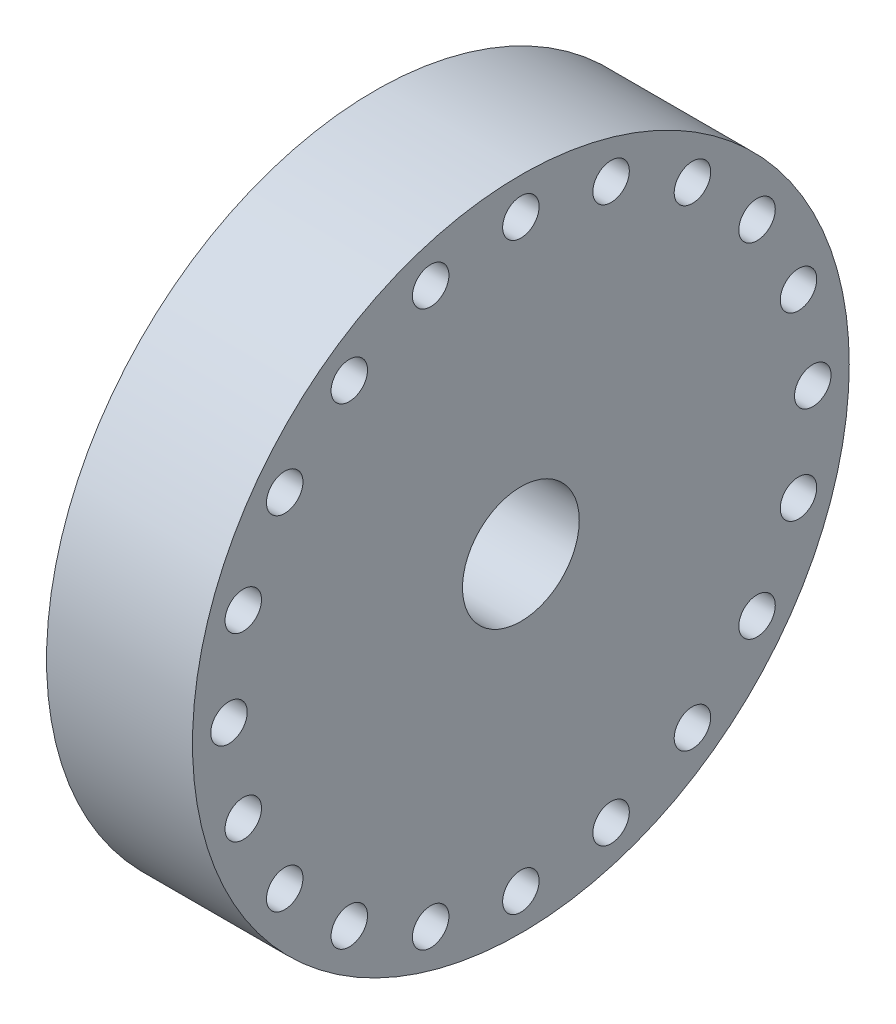
SolidWorks part; units mm, degrees
ref_plane "Front Plane" through (0, 0, 0) normal (0, 0, 1) x (1, 0, 0)
ref_plane "Top Plane" through (0, 0, 0) normal (0, 1, 0) x (1, 0, 0)
ref_plane "Right Plane" through (0, 0, 0) normal (1, 0, 0) x (0, 0, -1)
sketch "Sketch1" plane through (0, 0, 0) normal (1, 0, 0) x (0, 0, -1)
  circle A0 centre (0, 0) radius 7.1438
  circle A1 centre (0, 0) radius 6.35 construction
  circle A2 centre (0, 6.35) radius 0.3969
  circle A3 centre (1.9623, 6.0392) radius 0.3969
  circle A4 centre (3.7324, 5.1373) radius 0.3969
  circle A5 centre (5.1373, 3.7324) radius 0.3969
  circle A6 centre (6.0392, 1.9623) radius 0.3969
  circle A7 centre (6.35, 0) radius 0.3969
  circle A8 centre (6.0392, -1.9623) radius 0.3969
  circle A9 centre (5.1373, -3.7324) radius 0.3969
  circle A10 centre (3.7324, -5.1373) radius 0.3969
  circle A11 centre (1.9623, -6.0392) radius 0.3969
  circle A12 centre (0, -6.35) radius 0.3969
  circle A13 centre (-1.9623, -6.0392) radius 0.3969
  circle A14 centre (-3.7324, -5.1373) radius 0.3969
  circle A15 centre (-5.1373, -3.7324) radius 0.3969
  circle A16 centre (-6.0392, -1.9623) radius 0.3969
  circle A17 centre (-6.35, 0) radius 0.3969
  circle A18 centre (-6.0392, 1.9623) radius 0.3969
  circle A19 centre (-5.1373, 3.7324) radius 0.3969
  circle A20 centre (-3.7324, 5.1373) radius 0.3969
  circle A21 centre (-1.9623, 6.0392) radius 0.3969
  dimension "D1" = 20
  dimension "D2" = 14.2875
  dimension "D3" = 0.7937
  dimension "D4" = 12.7
extrude "Boss-Extrude1" add sketch "Sketch1" along normal blind 3.175
sketch "Sketch2" plane through (3.175, 0, 0) normal (1, 0, 0) x (0, 0, -1)
  circle A0 centre (0, 0) radius 1.27
  dimension "D1" = 2.54
extrude "Cut-Extrude1" cut sketch "Sketch2" against normal through all
sketch "Sketch3" plane through (3.175, 0, 0) normal (1, 0, 0) x (0, 0, -1)
  circle A0 centre (0, 0) radius 6.35 construction
  point P0 (0, 0)
